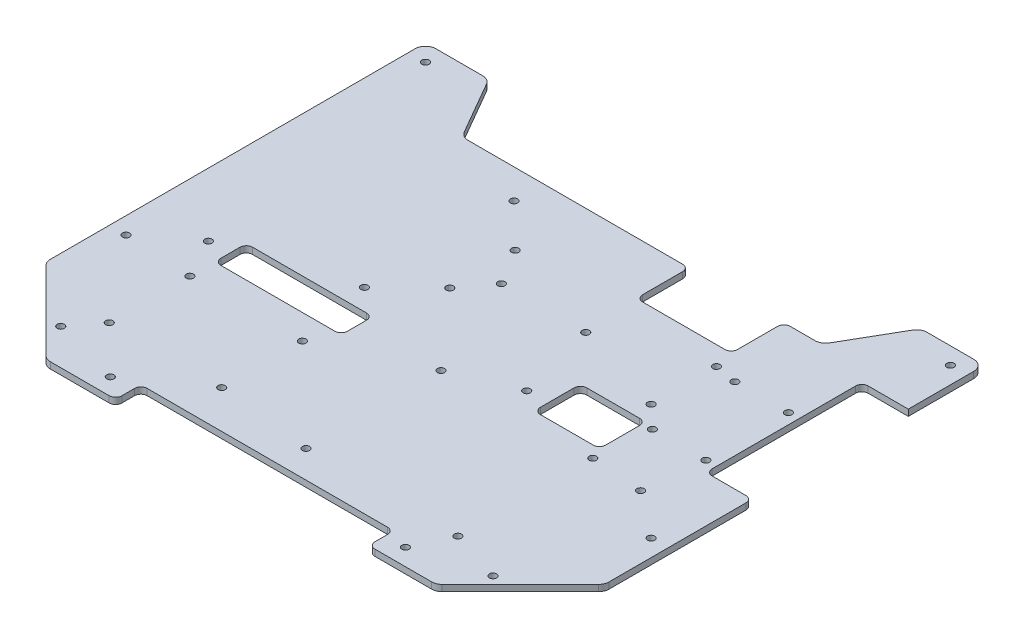
SolidWorks part; units mm, degrees
material "Acier non allié"
ref_plane "Front" through (0, 0, 0) normal (0, 0, 1) x (1, 0, 0)
ref_plane "Top" through (0, 0, 0) normal (0, 1, 0) x (1, 0, 0)
ref_plane "Right" through (0, 0, 0) normal (1, 0, 0) x (0, 0, -1)
sketch "Esquisse1" plane through (0, 0, 0) normal (0, 1, 0) x (1, 0, 0)
  line L0 (0, 0) -> (0, 190) construction
  line L1 (-92.5, 0) -> (92.5, 0)
  line L2 (92.5, 0) -> (132.5, 40)
  line L3 (132.5, 40) -> (132.5, 220)
  line L4 (132.5, 220) -> (102.5, 220)
  line L5 (102.5, 220) -> (85.1795, 190)
  line L6 (85.1795, 190) -> (-85.1795, 190)
  line L7 (-102.5, 220) -> (-85.1795, 190)
  line L8 (-132.5, 220) -> (-102.5, 220)
  line L9 (-132.5, 40) -> (-132.5, 220)
  line L10 (-92.5, 0) -> (-132.5, 40)
  dimension "D1" = 132.5
  dimension "D2" = 220
  dimension "D3" = 60
  dimension "D4" = 30
  dimension "D5" = 40
  dimension "D6" = 40
  dimension "D7" = 30
extrude "Boss.-Extru.1" add sketch "Esquisse1" along normal blind 3
fillet "Congé1" radius 5 10 edges at (92.5, 1.5, 0) (132.5, 1.5, -40) (132.5, 1.5, -220) (102.5, 1.5, -220) (85.1795, 1.5, -190) (-85.1795, 1.5, -190) (-102.5, 1.5, -220) (-132.5, 1.5, -220) (-92.5, 1.5, 0) (-132.5, 1.5, -40)
sketch "Esquisse2" plane through (0, 3, 0) normal (0, 1, 0) x (1, 0, 0)
  line L0 (0, 0) -> (0, 294.1173) construction
  line L2 (-90.4289, 0) -> (90.4289, 0) construction
  circle A0 centre (70, 8) radius 1
  circle A1 centre (124.5, 70) radius 1
  circle A2 centre (124.5, 212) radius 1
  circle A3 centre (-124.5, 212) radius 1
  circle A4 centre (-124.5, 70) radius 1
  circle A5 centre (-70, 8) radius 1
  dimension "D2" = 2
  dimension "D6" = 2
  dimension "D9" = 2
  dimension "D1" = 70
  dimension "D3" = 8
  dimension "D4" = 124.5
  dimension "D5" = 70
  dimension "D7" = 124.5
  dimension "D8" = 212
extrude "Enlèv. mat.-Extru.1" cut sketch "Esquisse2" against normal blind 3
hole_wizard "Dégagement M31" positions "Esquisse3" profile "Esquisse4" hole size "M3" standard "ISO" end condition through all
sketch "Esquisse3" plane through (0, 3, 0) normal (0, 1, 0) x (1, 0, 0)
  point P0 (70, 8)
  point P3 (-70, 8)
  point P6 (-124.5, 70)
  point P9 (-124.5, 212)
  point P12 (124.5, 212)
  point P15 (124.5, 70)
sketch "Esquisse4" plane through (70, 3, -8) normal (1, 0, 0) x (0, 0, 1)
  line L0 (0, 0) -> (0, 3)
  line L1 (0, 3) -> (1.7, 3)
  line L2 (1.7, 3) -> (1.7, 0)
  line L5 (1.7, 0) -> (0, 0)
  line L11 (0, -6.35) -> (0, 107.95) construction
  dimension "Diamètre du perçage jusqu'au prochain" = 3.4
  dimension "Profondeur du perçage jusqu'au prochain" = 3
sketch "Esquisse5" plane through (0, 3, 0) normal (0, 1, 0) x (1, 0, 0)
  line L0 (82.2927, 190) -> (-82.2927, 190) construction
  line L1 (67.5, 190) -> (22.5, 190)
  line L2 (67.5, 190) -> (67.5, 165)
  line L3 (67.5, 165) -> (22.5, 165)
  line L4 (22.5, 190) -> (22.5, 165)
  line L5 (132.5, 42.0711) -> (132.5, 215) construction
  line L6 (132.5, 184) -> (110.5, 184)
  line L7 (132.5, 184) -> (132.5, 110)
  line L8 (132.5, 110) -> (110.5, 110)
  line L9 (110.5, 184) -> (110.5, 110)
  line L10 (127.5, 220) -> (105.3868, 220) construction
  dimension "D1" = 25
  dimension "D2" = 65
  dimension "D3" = 110
  dimension "D4" = 36
  dimension "D5" = 110
  dimension "D6" = 22
extrude "Enlèv. mat.-Extru.2" cut sketch "Esquisse5" against normal through all
fillet "Congé2" radius 3 7 edges at (132.5, 1.5, -110) (110.5, 1.5, -110) (110.5, 1.5, -184) (67.5, 1.5, -190) (67.5, 1.5, -165) (22.5, 1.5, -165) (22.5, 1.5, -190)
sketch "Esquisse6" plane through (0, 3, 0) normal (0, 1, 0) x (1, 0, 0)
  line L0 (110.5, 140.5) -> (-167.6757, 140.5) construction
  line L1 (110.5, 181) -> (110.5, 113) construction
  line L2 (-90.4289, 0) -> (90.4289, 0) construction
  line L3 (110.5, 181) -> (110.5, 113) construction
  circle A0 centre (69.5, 156) radius 1
  circle A1 centre (-26, 156) radius 1
  circle A2 centre (-46.5, 176) radius 1
  circle A3 centre (69.5, 125) radius 1
  circle A4 centre (-26, 125) radius 1
  circle A5 centre (-46.5, 105) radius 1
  dimension "D4" = 2
  dimension "D6" = 2
  dimension "D10" = 2
  dimension "D1" = 140.5
  dimension "D2" = 41
  dimension "D3" = 15.5
  dimension "D5" = 136.5
  dimension "D7" = 15.5
  dimension "D8" = 35.5
  dimension "D9" = 157
extrude "Enlèv. mat.-Extru.3" cut sketch "Esquisse6" against normal through all
hole_wizard "Dégagement M32" positions "Esquisse7" profile "Esquisse8" hole size "M3" standard "ISO"
sketch "Esquisse7" plane through (0, 3, 0) normal (0, 1, 0) x (1, 0, 0)
  point P0 (-46.5, 105)
  point P3 (-26, 125)
  point P6 (-26, 156)
  point P9 (-46.5, 176)
  point P12 (69.5, 156)
  point P15 (69.5, 125)
sketch "Esquisse8" plane through (-46.5, 3, -105) normal (1, 0, 0) x (0, 0, 1)
  line L0 (0, 0) -> (0, 11.0215)
  line L1 (0, 11.0215) -> (1.7, 10)
  line L2 (1.7, 10) -> (1.7, 0)
  line L5 (1.7, 0) -> (0, 0)
  line L10 (0, 11.0215) -> (-1.7, 10) construction
  line L11 (0, -6.35) -> (0, 107.95) construction
  dimension "Diamètre du perçage" = 3.4
  dimension "Profondeur du perçage" = 10
  dimension "Angle de pointe" = 118
sketch "Esquisse9" plane through (0, 3, 0) normal (0, 1, 0) x (1, 0, 0)
  line L0 (132.5, 42.0711) -> (132.5, 107) construction
  line L1 (-90.4289, 0) -> (90.4289, 0) construction
  line L2 (-132.5, 215) -> (-132.5, 42.0711) construction
  line L3 (-39.16, 30) -> (-92.5, 30) construction
  line L4 (-39.16, 30) -> (-39.16, 68.24) construction
  line L5 (-39.16, 68.24) -> (-92.5, 68.24) construction
  line L6 (-92.5, 30) -> (-92.5, 68.24) construction
  line L7 (5.84, 25) -> (5.84, 89) construction
  line L8 (25.5, 165) -> (64.5, 165) construction
  line L9 (24.5, 139) -> (-15.5, 139) construction
  line L10 (110.5, 181) -> (110.5, 113) construction
  line L11 (113.5, 110) -> (129.5, 110) construction
  circle A0 centre (105.5, 115) radius 1
  circle A3 centre (105.5, 154.12) radius 1
  circle A6 centre (-92.5, 68.24) radius 1
  circle A7 centre (-39.16, 68.24) radius 1
  circle A8 centre (-39.16, 30) radius 1
  circle A9 centre (-92.5, 30) radius 1
  circle A10 centre (5.84, 89) radius 1
  circle A11 centre (77.84, 89) radius 1
  circle A12 centre (5.84, 25) radius 1
  circle A13 centre (77.84, 25) radius 1
  circle A14 centre (-15.5, 139) radius 1
  circle A15 centre (24.5, 139) radius 1
  circle A16 centre (34.5, 101) radius 1
  circle A17 centre (80.1, 115) radius 1
  circle A18 centre (80.1, 154.12) radius 1
  dimension "D2" = 2
  dimension "D4" = 2
  dimension "D17" = 2
  dimension "D18" = 2
  dimension "D19" = 2
  dimension "D20" = 2
  dimension "D21" = 2
  dimension "D22" = 2
  dimension "D23" = 2
  dimension "D24" = 2
  dimension "D32" = 2
  dimension "D33" = 2
  dimension "D34" = 2
  dimension "D11" = 2
  dimension "D12" = 2
  dimension "D5" = 27
  dimension "25" = 27
  dimension "D10" = 39.12
  dimension "D13" = 38.24
  dimension "D14" = 53.34
  dimension "D15" = 30
  dimension "D16" = 40
  dimension "D25" = 72
  dimension "D26" = 72
  dimension "D27" = 64
  dimension "D28" = 64
  dimension "D29" = 45
  dimension "D30" = 25
  dimension "D31" = 25
  dimension "D37" = 40
  dimension "D39" = 10
  dimension "D7" = 5
  dimension "D8" = 25.4
  dimension "D9" = 25.4
  dimension "D40" = 39.12
  dimension "D38" = 76
  dimension "D6" = 38
  dimension "D35" = 26
extrude "Enlèv. mat.-Extru.4" cut sketch "Esquisse9" against normal through all
hole_wizard "Dégagement M33" positions "Esquisse10" profile "Esquisse11" hole size "M3" standard "ISO"
sketch "Esquisse10" plane through (0, 3, 0) normal (0, 1, 0) x (1, 0, 0)
  point P3 (105.5, 115)
  point P9 (105.5, 154.12)
  point P14 (80.1, 154.12)
  point P17 (80.1, 115)
sketch "Esquisse11" plane through (105.5, 3, -115) normal (1, 0, 0) x (0, 0, 1)
  line L0 (0, 0) -> (0, 11.0215)
  line L1 (0, 11.0215) -> (1.7, 10)
  line L2 (1.7, 10) -> (1.7, 0)
  line L5 (1.7, 0) -> (0, 0)
  line L10 (0, 11.0215) -> (-1.7, 10) construction
  line L11 (0, -6.35) -> (0, 107.95) construction
  dimension "Diamètre du perçage" = 3.4
  dimension "Profondeur du perçage" = 10
  dimension "Angle de pointe" = 118
sketch "Esquisse12" plane through (0, 3, 0) normal (0, 1, 0) x (1, 0, 0)
  line L2 (-90.4289, 0) -> (90.4289, 0) construction
  line L3 (102.5, 17) -> (-102.5, 17) construction
  line L4 (102.5, 17) -> (102.5, 87) construction
  line L5 (102.5, 87) -> (-102.5, 87) construction
  line L6 (-102.5, 17) -> (-102.5, 87) construction
  line L7 (132.5, 42.0711) -> (132.5, 107) construction
  circle A4 centre (-102.5, 87) radius 1
  circle A5 centre (102.5, 87) radius 1
  circle A6 centre (102.5, 17) radius 1
  circle A7 centre (-102.5, 17) radius 1
  point P6 (102.5, 52)
  dimension "D5" = 2
  dimension "D6" = 2
  dimension "D7" = 2
  dimension "D8" = 2
  dimension "D1" = 70
  dimension "D2" = 205
  dimension "D3" = 17
  dimension "D4" = 30
extrude "Enlèv. mat.-Extru.5" cut sketch "Esquisse12" against normal through all and the other way through all
hole_wizard "Dégagement M34" positions "Esquisse13" profile "Esquisse14" hole size "M3" standard "ISO"
sketch "Esquisse13" plane through (0, 3, 0) normal (0, 1, 0) x (1, 0, 0)
  point P3 (-92.5, 68.24)
  point P6 (-92.5, 30)
  point P9 (-39.16, 30)
  point P12 (-39.16, 68.24)
  point P16 (5.84, 25)
  point P19 (77.84, 25)
  point P22 (5.84, 89)
  point P25 (77.84, 89)
  point P29 (34.5, 101)
  point P32 (24.5, 139)
  point P35 (-15.5, 139)
sketch "Esquisse14" plane through (-92.5, 3, -68.24) normal (1, 0, 0) x (0, 0, 1)
  line L0 (0, 0) -> (0, 11.0215)
  line L1 (0, 11.0215) -> (1.7, 10)
  line L2 (1.7, 10) -> (1.7, 0)
  line L5 (1.7, 0) -> (0, 0)
  line L10 (0, 11.0215) -> (-1.7, 10) construction
  line L11 (0, -6.35) -> (0, 107.95) construction
  dimension "Diamètre du perçage" = 3.4
  dimension "Profondeur du perçage" = 10
  dimension "Angle de pointe" = 118
hole_wizard "Dégagement M35" positions "Esquisse15" profile "Esquisse16" hole size "M3" standard "ISO"
sketch "Esquisse15" plane through (0, 3, 0) normal (0, 1, 0) x (1, 0, 0)
  point P0 (-102.5, 17)
  point P3 (-102.5, 87)
  point P6 (102.5, 87)
  point P9 (102.5, 17)
sketch "Esquisse16" plane through (-102.5, 3, -17) normal (1, 0, 0) x (0, 0, 1)
  line L0 (0, 0) -> (0, 11.0215)
  line L1 (0, 11.0215) -> (1.7, 10)
  line L2 (1.7, 10) -> (1.7, 0)
  line L5 (1.7, 0) -> (0, 0)
  line L10 (0, 11.0215) -> (-1.7, 10) construction
  line L11 (0, -6.35) -> (0, 107.95) construction
  dimension "Diamètre du perçage" = 3.4
  dimension "Profondeur du perçage" = 10
  dimension "Angle de pointe" = 118
sketch "Esquisse17" plane through (0, 3, 0) normal (0, 1, 0) x (1, 0, 0)
  line L0 (-90.4289, 0) -> (90.4289, 0) construction
  line L1 (-92.5, 95) -> (-32.5, 95)
  line L2 (-92.5, 95) -> (-92.5, 80)
  line L3 (-92.5, 80) -> (-32.5, 80)
  line L4 (-32.5, 95) -> (-32.5, 80)
  line L5 (-132.5, 215) -> (-132.5, 42.0711) construction
  line L6 (132.5, 42.0711) -> (132.5, 107) construction
  line L7 (44.5, 116.5) -> (75.5, 116.5)
  line L8 (44.5, 116.5) -> (44.5, 94.5)
  line L9 (44.5, 94.5) -> (75.5, 94.5)
  line L10 (75.5, 116.5) -> (75.5, 94.5)
  line L11 (82.2927, 190) -> (70.5, 190) construction
  line L13 (-59.5, 12) -> (60.5, 12)
  line L14 (-59.5, 12) -> (-59.5, 0)
  line L15 (-59.5, 0) -> (60.5, 0)
  line L16 (60.5, 12) -> (60.5, 0)
  dimension "D1" = 60
  dimension "D2" = 15
  dimension "D3" = 80
  dimension "D4" = 40
  dimension "D5" = 31
  dimension "D6" = 22
  dimension "D7" = 57
  dimension "D8" = 73.5
  dimension "D9" = 12
  dimension "D11" = 120
  dimension "D12" = 72
extrude "Enlèv. mat.-Extru.6" cut sketch "Esquisse17" against normal up to surface (3 mm away) up to face at (-102.5, 0, -15.3)
fillet "Congé3" radius 3 12 edges at (60.5, 1.5, 0) (60.5, 1.5, -12) (-59.5, 1.5, -12) (-59.5, 1.5, 0) (44.5, 1.5, -116.5) (75.5, 1.5, -116.5) (75.5, 1.5, -94.5) (44.5, 1.5, -94.5) (-92.5, 1.5, -80) (-32.5, 1.5, -80) (-32.5, 1.5, -95) (-92.5, 1.5, -95)
equation "\"WIDTH\"= 300mm'Total width of the robot"
equation "\"LENGTH\"= 220mm'Total length of the robot"
equation "\"CUT_DEPTH\"= 45mm'Depth of the cut on the edges of the plate"
equation "\"Plate_th\"= 3mm'Thickness of the plate"
equation "\"D1\"= \"Plate_th\""
equation "\"D5@Esquisse9\"=\"25@Esquisse9\""
